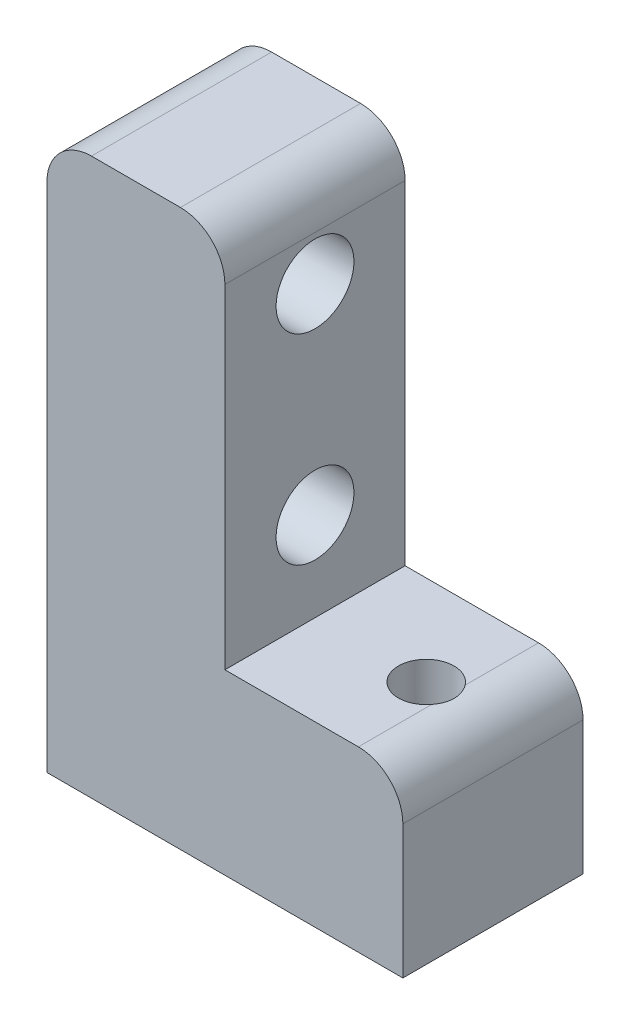
SolidWorks part; units mm, degrees
ref_plane "Plan de face" through (0, 0, 0) normal (0, 0, 1) x (1, 0, 0)
ref_plane "Plan de dessus" through (0, 0, 0) normal (0, 1, 0) x (1, 0, 0)
ref_plane "Plan de droite" through (0, 0, 0) normal (1, 0, 0) x (0, 0, -1)
sketch "Esquisse1" plane through (0, 0, 0) normal (0, 0, 1) x (1, 0, 0)
  line L1 (0, 0) -> (16, 0)
  line L2 (0, 0) -> (0, 25)
  line L3 (0, 25) -> (16, 25)
  line L4 (16, 0) -> (16, 25)
  dimension "D1" = 16
  dimension "D2" = 25
extrude "Boss.-Extru.1" add sketch "Esquisse1" along normal blind 8.1
sketch "Esquisse2" plane through (0, 0, 0) normal (0, -1, 0) x (1, 0, 0)
  line L0 (8, 8.1) -> (8, 0) construction
  line L1 (0, 8.1) -> (16, 8.1) construction
  line L2 (0, 0) -> (16, 0) construction
  line L3 (16, 4.05) -> (0, 4.05) construction
  line L4 (16, 8.1) -> (16, 0) construction
  line L5 (0, 8.1) -> (0, 0) construction
  circle A0 centre (3, 4.05) radius 1.25
  circle A1 centre (13, 4.05) radius 1.25
  dimension "D1" = 10
  dimension "D2" = 2.5
extrude "Enlèv. mat.-Extru.1" cut sketch "Esquisse2" against normal blind 8
sketch "Esquisse3" plane through (0, 0, 0) normal (-1, 0, 0) x (0, 0, 1)
  line L0 (4.05, 0) -> (4.05, 21) construction
  line L1 (8.1, 0) -> (0, 0) construction
  circle A0 centre (4.05, 21) radius 1.75
  circle A1 centre (4.05, 12) radius 1.75
  dimension "D1" = 3.5
  dimension "D2" = 9
  dimension "D3" = 12
extrude "Enlèv. mat.-Extru.2" cut sketch "Esquisse3" against normal blind 8
sketch "Esquisse4" plane through (0, 0, 8.1) normal (0, 0, 1) x (1, 0, 0)
  line L0 (0, 25) -> (0, 0) construction
  line L1 (16, 25) -> (8, 25)
  line L2 (16, 25) -> (16, 8)
  line L3 (16, 8) -> (8, 8)
  line L4 (8, 25) -> (8, 8)
  line L5 (0, 0) -> (16, 0) construction
  dimension "D1" = 8
  dimension "D2" = 8
extrude "Enlèv. mat.-Extru.3" cut sketch "Esquisse4" against normal through all
fillet "Congé1" radius 2 3 edges at (16, 8, 4.05) (0, 25, 4.05) (8, 25, 4.05)
